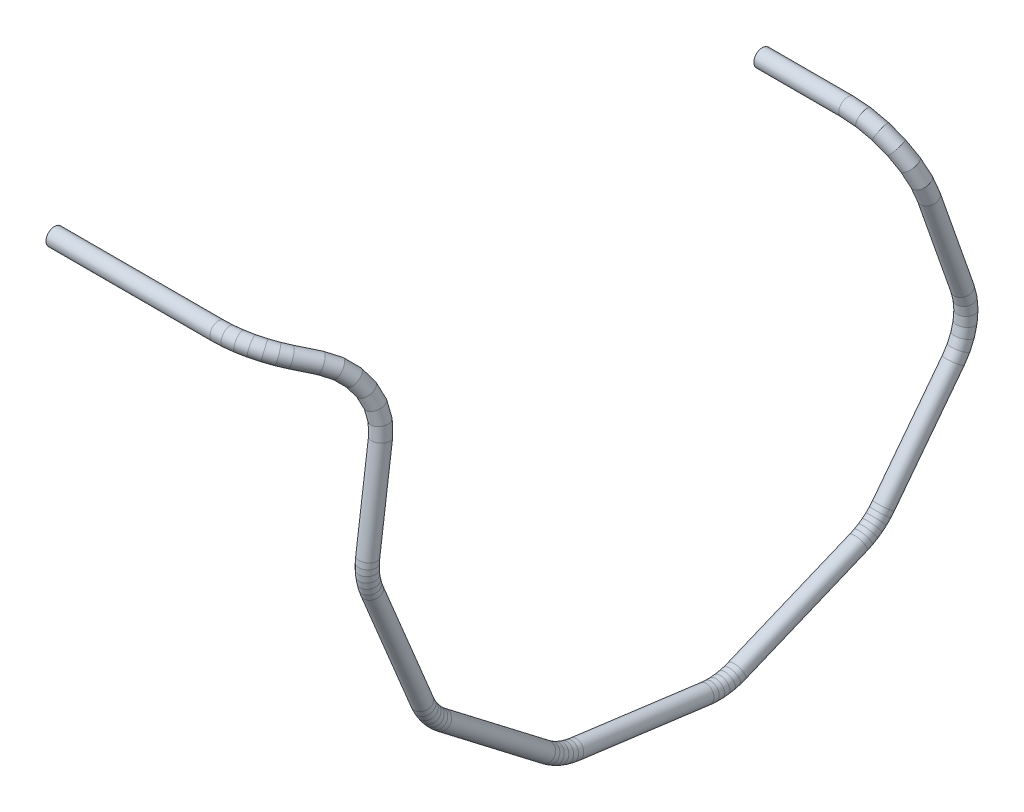
SolidWorks part; units mm, degrees
ref_plane "Front Plane" through (0, 0, 0) normal (0, 0, 1) x (1, 0, 0)
ref_plane "Top Plane" through (0, 0, 0) normal (0, 1, 0) x (1, 0, 0)
ref_plane "Right Plane" through (0, 0, 0) normal (1, 0, 0) x (0, 0, -1)
sketch3d "Path"
  line L0 (-571, 44.8888, 108.3711) -> (-523.0671, 44.8888, 108.3711)
  line L1 (-523.0671, 44.8888, 108.3711) -> (-520.2786, 44.8056, 108.1703)
  line L2 (-520.2786, 44.8056, 108.1703) -> (-517.5575, 44.5581, 107.5729)
  line L3 (-517.5575, 44.5581, 107.5729) -> (-514.9693, 44.1524, 106.5932)
  line L4 (-514.9693, 44.1524, 106.5932) -> (-512.5767, 43.598, 105.2549)
  line L5 (-512.5767, 43.598, 105.2549) -> (-510.4374, 42.9086, 103.5904)
  line L6 (-510.4374, 42.9086, 103.5904) -> (-508.603, 42.1006, 101.6398)
  line L7 (-508.603, 42.1006, 101.6398) -> (-504.6755, 40.0715, 96.7412)
  line L8 (-504.6755, 40.0715, 96.7412) -> (-502.3239, 38.389, 93.8697)
  line L9 (-502.3239, 38.389, 93.8697) -> (-500.2095, 35.918, 91.4141)
  line L10 (-500.2095, 35.918, 91.4141) -> (-498.4408, 32.785, 89.5003)
  line L11 (-498.4408, 32.785, 89.5003) -> (-497.1085, 29.1506, 88.2264)
  line L12 (-497.1085, 29.1506, 88.2264) -> (-496.2807, 25.2012, 87.6577)
  line L13 (-496.2807, 25.2012, 87.6577) -> (-496, 21.1391, 87.8232)
  line L14 (-496, 21.1391, 87.8232) -> (-496, -7.3571, 91.5748)
  line L15 (-496, -7.3571, 91.5748) -> (-496, -8.9214, 91.7117)
  line L16 (-496, -8.9214, 91.7117) -> (-496, -10.4917, 91.7117)
  line L17 (-496, -10.4917, 91.7117) -> (-496, -12.0561, 91.5748)
  line L18 (-496, -12.0561, 91.5748) -> (-496, -13.6025, 91.3022)
  line L19 (-496, -13.6025, 91.3022) -> (-496, -15.1193, 90.8957)
  line L20 (-496, -15.1193, 90.8957) -> (-496, -16.5949, 90.3587)
  line L21 (-496, -16.5949, 90.3587) -> (-496, -52.1589, 75.6276)
  line L22 (-496, -52.1589, 75.6276) -> (-496, -53.582, 74.9639)
  line L23 (-496, -53.582, 74.9639) -> (-496, -54.942, 74.1788)
  line L24 (-496, -54.942, 74.1788) -> (-496, -56.2283, 73.2781)
  line L25 (-496, -56.2283, 73.2781) -> (-496, -57.4312, 72.2687)
  line L26 (-496, -57.4312, 72.2687) -> (-496, -58.5416, 71.1584)
  line L27 (-496, -58.5416, 71.1584) -> (-496, -59.5509, 69.9554)
  line L28 (-496, -59.5509, 69.9554) -> (-496, -82.9847, 39.416)
  line L29 (-496, -82.9847, 39.416) -> (-496, -83.8854, 38.1297)
  line L30 (-496, -83.8854, 38.1297) -> (-496, -84.6705, 36.7697)
  line L31 (-496, -84.6705, 36.7697) -> (-496, -85.3342, 35.3466)
  line L32 (-496, -85.3342, 35.3466) -> (-496, -85.8712, 33.871)
  line L33 (-496, -85.8712, 33.871) -> (-496, -86.2777, 32.3542)
  line L34 (-496, -86.2777, 32.3542) -> (-496, -86.5503, 30.8077)
  line L35 (-496, -86.5503, 30.8077) -> (-496, -91.5748, -7.3571)
  line L36 (-496, -91.5748, -7.3571) -> (-496, -91.7117, -8.9214)
  line L37 (-496, -91.7117, -8.9214) -> (-496, -91.7117, -10.4917)
  line L38 (-496, -91.7117, -10.4917) -> (-496, -91.5748, -12.0561)
  line L39 (-496, -91.5748, -12.0561) -> (-496, -91.3022, -13.6025)
  line L40 (-496, -91.3022, -13.6025) -> (-496, -90.8957, -15.1193)
  line L41 (-496, -90.8957, -15.1193) -> (-496, -90.3587, -16.5949)
  line L42 (-496, -90.3587, -16.5949) -> (-496, -75.6276, -52.1589)
  line L43 (-496, -75.6276, -52.1589) -> (-496, -74.9639, -53.582)
  line L44 (-496, -74.9639, -53.582) -> (-496, -74.1788, -54.942)
  line L45 (-496, -74.1788, -54.942) -> (-496, -73.2781, -56.2283)
  line L46 (-496, -73.2781, -56.2283) -> (-496, -72.2687, -57.4312)
  line L47 (-496, -72.2687, -57.4312) -> (-496, -71.1584, -58.5416)
  line L48 (-496, -71.1584, -58.5416) -> (-496, -69.9554, -59.5509)
  line L49 (-496, -69.9554, -59.5509) -> (-496, -43.3123, -79.995)
  line L50 (-496, -43.3123, -79.995) -> (-496, -40.8139, -81.6029)
  line L51 (-496, -40.8139, -81.6029) -> (-496, -38.0851, -82.778)
  line L52 (-496, -38.0851, -82.778) -> (-496, -35.2001, -83.4883)
  line L53 (-496, -35.2001, -83.4883) -> (-496, -32.2376, -83.7142)
  line L54 (-496, -32.2376, -83.7142) -> (-496, -29.2783, -83.4498)
  line L55 (-496, -29.2783, -83.4498) -> (-496, -26.4028, -82.7021)
  line L56 (-496, -26.4028, -82.7021) -> (-496, 1.7124, -72.8517)
  line L57 (-496, 1.7124, -72.8517) -> (-496.6133, 6.1092, -71.3113)
  line L58 (-496.6133, 6.1092, -71.3113) -> (-498.4115, 10.2062, -69.8759)
  line L59 (-498.4115, 10.2062, -69.8759) -> (-501.2721, 13.7245, -68.6432)
  line L60 (-501.2721, 13.7245, -68.6432) -> (-505, 16.4241, -67.6974)
  line L61 (-505, 16.4241, -67.6974) -> (-509.3413, 18.1212, -67.1028)
  line L62 (-509.3413, 18.1212, -67.1028) -> (-514, 18.7, -66.9)
  line L63 (-514, 18.7, -66.9) -> (-538.85, 18.7, -66.9)
ref_plane "Start Plane" through (-571, 0, 0) normal (1, 0, 0) x (0, 0, -1)
sketch "Profile" plane through (-571, 0, 0) normal (1, 0, 0) x (0, 0, -1)
  circle A0 centre (-108.3711, 44.8888) radius 2.5
  circle A1 centre (-108.3711, 44.8888) radius 1
sweep "Tube" add profiles "Profile" path "Path"
ref_axis "Engine Axis" through (-489.625, 0, 0) along (-1, 0, 0)
